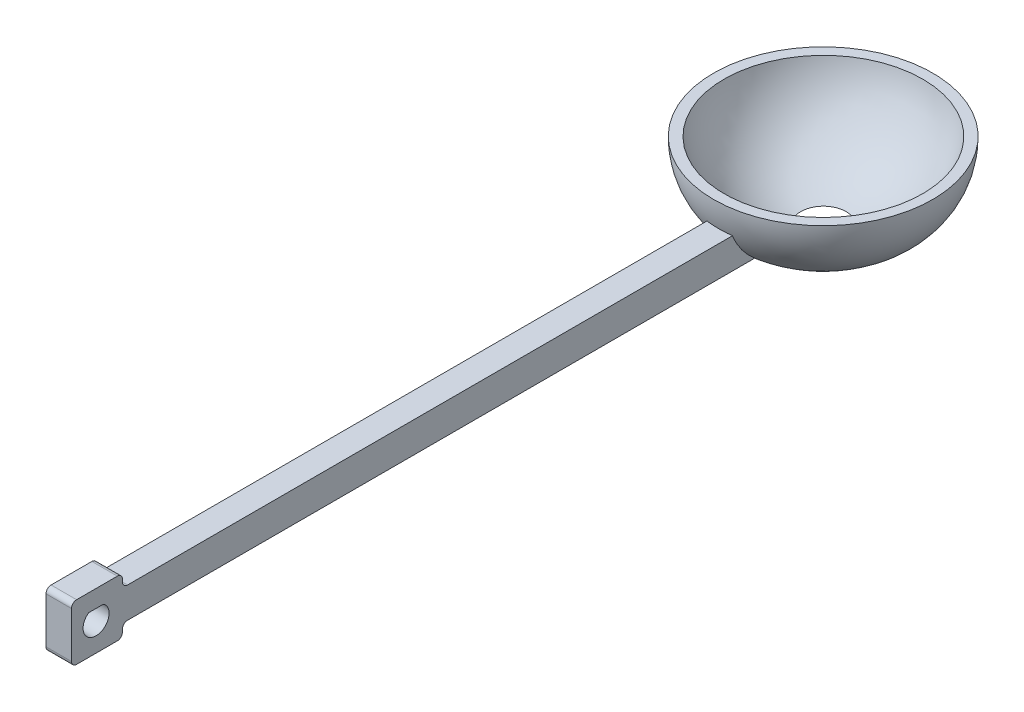
SolidWorks part; units mm, degrees
ref_plane "Front Plane" through (0, 0, 0) normal (0, 0, 1) x (1, 0, 0)
ref_plane "Top Plane" through (0, 0, 0) normal (0, 1, 0) x (1, 0, 0)
ref_plane "Right Plane" through (0, 0, 0) normal (1, 0, 0) x (0, 0, -1)
sketch "Sketch1" plane through (0, 0, 0) normal (0, 1, 0) x (1, 0, 0)
  circle A0 centre (0, 0) radius 21.5
  dimension "D1" = 43
extrude "Boss-Extrude1" add sketch "Sketch1" along normal blind 30
sketch "Sketch2" plane through (0, 0, 0) normal (0, 0, 1) x (1, 0, 0)
  line L0 (-21.5, 30) -> (-21.5, 0) construction
  line L1 (-2.5, 20) -> (2.5, 20)
  line L2 (-2.5, 20) -> (-2.5, 14)
  line L3 (-2.5, 14) -> (2.5, 14)
  line L4 (2.5, 20) -> (2.5, 14)
  line L5 (21.5, 0) -> (21.5, 30) construction
  line L6 (21.5, 30) -> (-21.5, 30) construction
  line L7 (-21.5, 0) -> (21.5, 0) construction
  dimension "D1" = 19
  dimension "D2" = 19
  dimension "D3" = 10
  dimension "D4" = 14
extrude "Boss-Extrude2" add sketch "Sketch2" along normal blind 150
sketch "Sketch6" plane through (0, 30, 0) normal (0, 1, 0) x (1, 0, 0)
  line L0 (-19.9553, 0) -> (20.0447, 0)
  arc A0 (-19.9553, 0) -> (20.0447, 0) centre (0.0447, 0) ccw
  dimension "D1" = 20
ref_axis "Axis3" through (-19.9553, 30, 0) along (1, 0, 0)
revolve "Cut-Revolve4" cut sketch "Sketch6" angle 360 about L0
sketch "Sketch7" plane through (0, 0, 0) normal (1, 0, 0) x (0, 0, -1)
  line L0 (-150, 20) -> (-21.3542, 20) construction
  line L1 (21.7835, -10.5) -> (-21.7835, -10.5)
  line L2 (21.7835, -10.5) -> (21.7835, 10.5)
  line L3 (21.7835, 10.5) -> (-21.7835, 10.5)
  line L4 (-21.7835, -10.5) -> (-21.7835, 10.5)
  line L5 (21.7835, -10.5) -> (-21.7835, 10.5) construction
  line L6 (21.7835, 10.5) -> (-21.7835, -10.5) construction
  point P0 (0, 0)
  dimension "D1" = 9.5
extrude "Cut-Extrude1" cut sketch "Sketch7" against normal through all both and the other way through all
sketch "Sketch8" plane through (2.5, 0, 0) normal (1, 0, 0) x (0, 0, -1)
  line L0 (-146.6208, 19.1) -> (-143.7277, 19.1)
  line L1 (-150, 14) -> (-21.3542, 14) construction
  arc A0 (-146.6208, 19.1) -> (-143.7277, 19.1) centre (-145.1743, 17) ccw
  dimension "D1" = 5.1
  dimension "D2" = 2.1
  dimension "D3" = 3
extrude "Cut-Extrude2" cut sketch "Sketch8" against normal blind 150
fillet "Fillet1" radius 3 1 edges at (0, 30, 21.5)
fillet "Fillet2" radius 15 1 edges at (0, 10.5, 21.5)
sketch "Sketch9" plane through (0, 20, 0) normal (0, 1, 0) x (1, 0, 0)
  line L0 (-2.5, -150) -> (-2.5, -20.3019) construction
  line L1 (2.5, -150) -> (-2.5, -150)
  line L2 (2.5, -150) -> (2.5, -140)
  line L3 (2.5, -140) -> (-2.5, -140)
  line L4 (-2.5, -150) -> (-2.5, -140)
  dimension "D1" = 10
extrude "Boss-Extrude3" add sketch "Sketch9" along normal blind 2.5
sketch "Sketch10" plane through (0, 14, 0) normal (0, -1, 0) x (1, 0, 0)
  line L0 (2.5, 150) -> (2.5, 15.9358) construction
  line L1 (-2.5, 150) -> (2.5, 150)
  line L2 (-2.5, 150) -> (-2.5, 140)
  line L3 (-2.5, 140) -> (2.5, 140)
  line L4 (2.5, 150) -> (2.5, 140)
  dimension "D1" = 10
extrude "Boss-Extrude4" add sketch "Sketch10" along normal blind 2.5
fillet "Fillet3" radius 1 6 edges at (0, 14, 140) (0, 11.5, 140) (0, 11.5, 150) (0, 22.5, 150) (0, 22.5, 140) (0, 20, 140)
sketch "Sketch11" plane through (0, 0, 0) normal (1, 0, 0) x (0, 0, -1)
  line L0 (-20, 30) -> (20, 30) construction
  line L1 (-39.3832, 37) -> (36.4795, 37)
  line L2 (-39.3832, 37) -> (-39.3832, 25.5)
  line L3 (-39.3832, 25.5) -> (36.4795, 25.5)
  line L4 (36.4795, 37) -> (36.4795, 25.5)
  dimension "D1" = 11.5
  dimension "D2" = 7
extrude "Cut-Extrude3" cut sketch "Sketch11" against normal through all both and the other way through all
